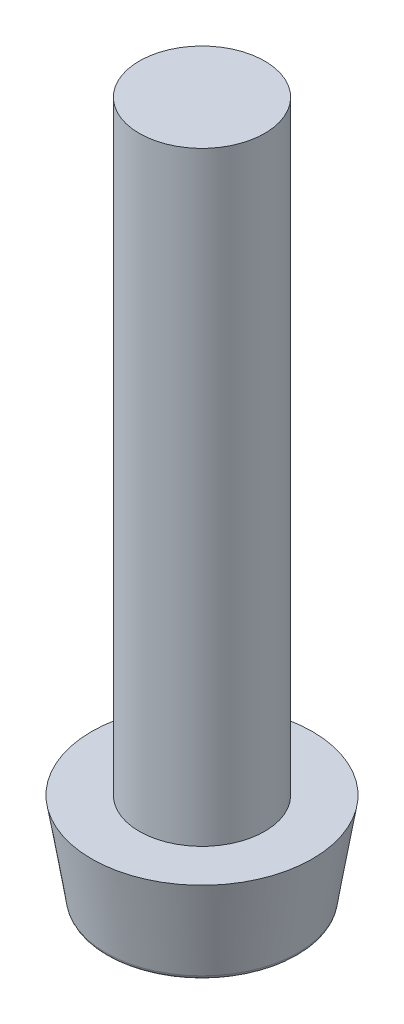
SolidWorks part; units mm, degrees
material "Nylon 101"
ref_plane "Plan de face" through (0, 0, 0) normal (0, 0, 1) x (1, 0, 0)
ref_plane "Plan de dessus" through (0, 0, 0) normal (0, 1, 0) x (1, 0, 0)
ref_plane "Plan de droite" through (0, 0, 0) normal (1, 0, 0) x (0, 0, -1)
sketch "Esquisse1" plane through (0, 0, 0) normal (0, 1, 0) x (1, 0, 0)
  circle A0 centre (0, 0) radius 2.2
  dimension "D1" = 4.4
extrude "Boss.-Extru.1" add sketch "Esquisse1" along normal blind 1.85
sketch "Esquisse2" plane through (0, 1.85, 0) normal (0, 1, 0) x (1, 0, 0)
  circle A0 centre (0, 0) radius 1.25
  dimension "D1" = 2.5
extrude "Boss.-Extru.2" add sketch "Esquisse2" along normal blind 12.05
chamfer "Chanfrein1" distance 0.3 distance2 1.85 1 edges at (0, 0, 2.2) first distance on face at (0, 0, 2.2)
fillet "Congé1" radius 0.1 1 edges at (0, 0, 1.9)
